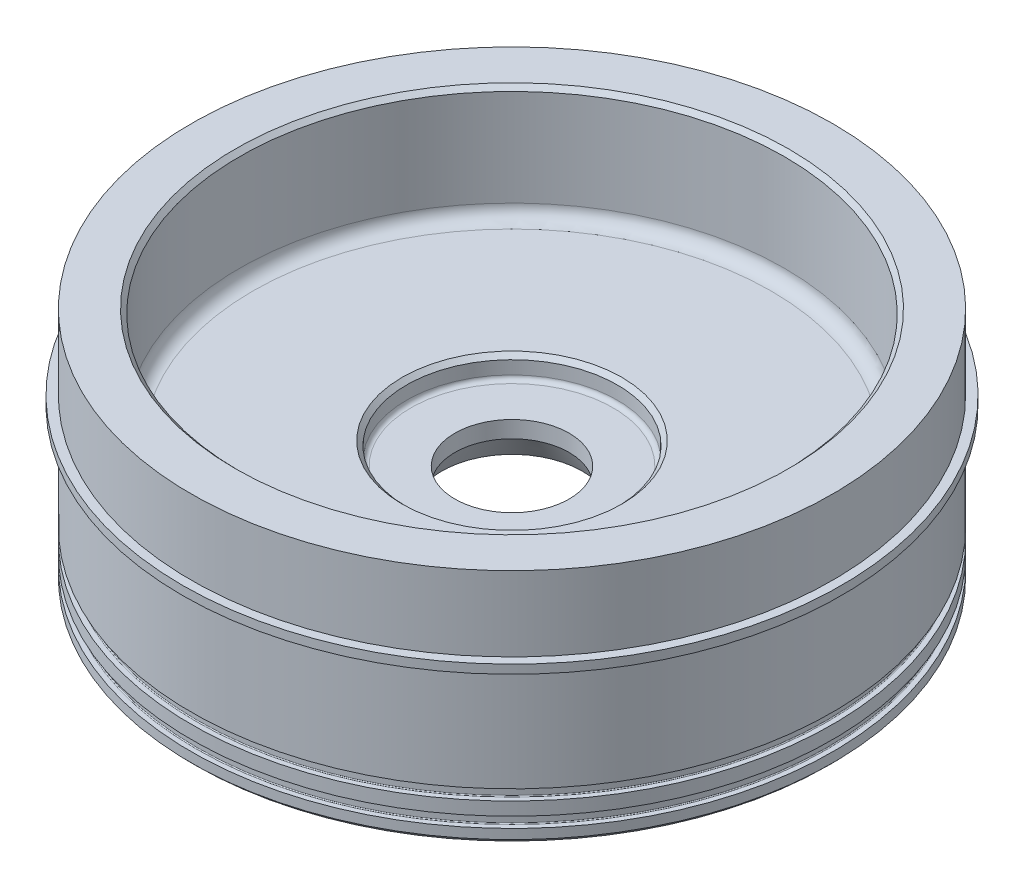
SolidWorks part; units mm, degrees
material "6061-T6 (SS)"
ref_plane "Piano frontale" through (0, 0, 0) normal (0, 0, 1) x (1, 0, 0)
ref_plane "Piano superiore" through (0, 0, 0) normal (0, 1, 0) x (1, 0, 0)
ref_plane "Piano destro" through (0, 0, 0) normal (1, 0, 0) x (0, 0, -1)
sketch "Schizzo1" plane through (0, 0, 0) normal (0, 0, 1) x (1, 0, 0)
  line L0 (0, 0) -> (0, 25.5769) construction
  line L1 (-13, 0) -> (-73, 0)
  line L2 (-73, 0) -> (-73, 14)
  line L3 (-73, 14) -> (-24, 14) construction
  line L4 (-24, 14) -> (-24, 9)
  line L5 (-24, 9) -> (-13, 9)
  line L6 (-13, 9) -> (-13, 0)
  line L7 (-24, 14) -> (-13, 14)
  line L8 (-13, 14) -> (-13, 9)
  line L9 (-73, 14) -> (-73, 40)
  line L10 (-73, 40) -> (-68, 40)
  line L11 (-69, 0) -> (-69, -14)
  line L12 (-69, -14) -> (-73, -14)
  line L13 (-73, -14) -> (-73, 0)
  line L14 (-68, 14) -> (-68, 40) construction
  line L15 (-73, 23) -> (-75, 23)
  line L16 (-75, 23) -> (-75, 21)
  line L17 (-73, -14) -> (-73, 0)
  line L18 (-73, -3) -> (-71.7, -3)
  line L19 (-71.7, -3) -> (-71.7, -5.4)
  line L20 (-71.7, -5.4) -> (-73, -5.4)
  line L21 (-73, -8.4) -> (-71.7, -8.4)
  line L22 (-71.7, -8.4) -> (-71.7, -10.8)
  line L23 (-71.7, -10.8) -> (-73, -10.8)
  line L24 (-75, 21) -> (-73, 21)
  line L25 (-68, 24) -> (-62, 24) construction
  line L26 (-62, 24) -> (-62, 22)
  line L27 (-62, 22) -> (-68, 22) construction
  line L28 (-62, 24) -> (-62, 40)
  line L29 (-62, 40) -> (-68, 40)
  line L30 (-62, 22) -> (-62, 14)
  line L31 (-62, 14) -> (-24, 14)
  dimension "D1" = 5
  dimension "D2" = 146
  dimension "D3" = 26
  dimension "D4" = 48
  dimension "D5" = 14
  dimension "D6" = 4
  dimension "D7" = 2.4
  dimension "D8" = 1.3
  dimension "D9" = 3
  dimension "D10" = 3
  dimension "D11" = 14
  dimension "D12" = 26
  dimension "D13" = 68
  dimension "D14" = 2
  dimension "D15" = 150
  dimension "D16" = 35
  dimension "D17" = 2
  dimension "D18" = 124
  dimension "D19" = 16
revolve "Rivoluzione1" add sketch "Schizzo1" angle 360 about L0 region at (-50.8007, 12.1097, 0) region at (-70.8307, -7.0125, 0) region at (-18.5, 11.5, 0) region at (-74, 22, 0)
chamfer "Smusso1" distance 3 angle 60 1 edges at (0, 0, -13) first distance on face at (0, 0, -69)
chamfer "Smusso2" distance 1 angle 45 1 edges at (0, -14, -69)
fillet "Raccordo1" radius 26 1 edges at (0, 0, -69)
chamfer "Smusso3" distance 1 angle 45 1 edges at (0, 40, -62)
fillet "Raccordo2" radius 0.2 4 edges at (0, -8.4, -71.7) (0, -10.8, -71.7) (0, -3, -71.7) (0, -5.4, -71.7)
sketch "Schizzo2" plane through (0, 0, 0) normal (0, 0, 1) x (1, 0, 0)
  line L0 (0, 0) -> (0, 58.1242) construction
  line L1 (0, 0) -> (-27.2443, 0) construction
  line L2 (-46.4833, 0) -> (46.4833, 0) construction
  line L3 (-13, 9) -> (-24, 9)
  line L4 (-24, 9) -> (-24, 14)
  line L6 (-24, 14) -> (-13, 14)
  line L7 (13, 14) -> (-13, 14) construction
  line L8 (-13, 14) -> (-13, 9)
  line L9 (-13, 9) -> (-13, 0) construction
  dimension "D1" = 5
  dimension "D2" = 48
revolve "Taglia-Rivoluzione1" cut sketch "Schizzo2" angle 360 about L0
fillet "Raccordo3" radius 1 1 edges at (0, 9, -24)
chamfer "Smusso4" distance 1 angle 45 1 edges at (0, 14, -24)
fillet "Raccordo4" radius 3 1 edges at (0, 14, -62)
chamfer "Smusso5" distance 1 angle 45 1 edges at (0, -14, -73)
